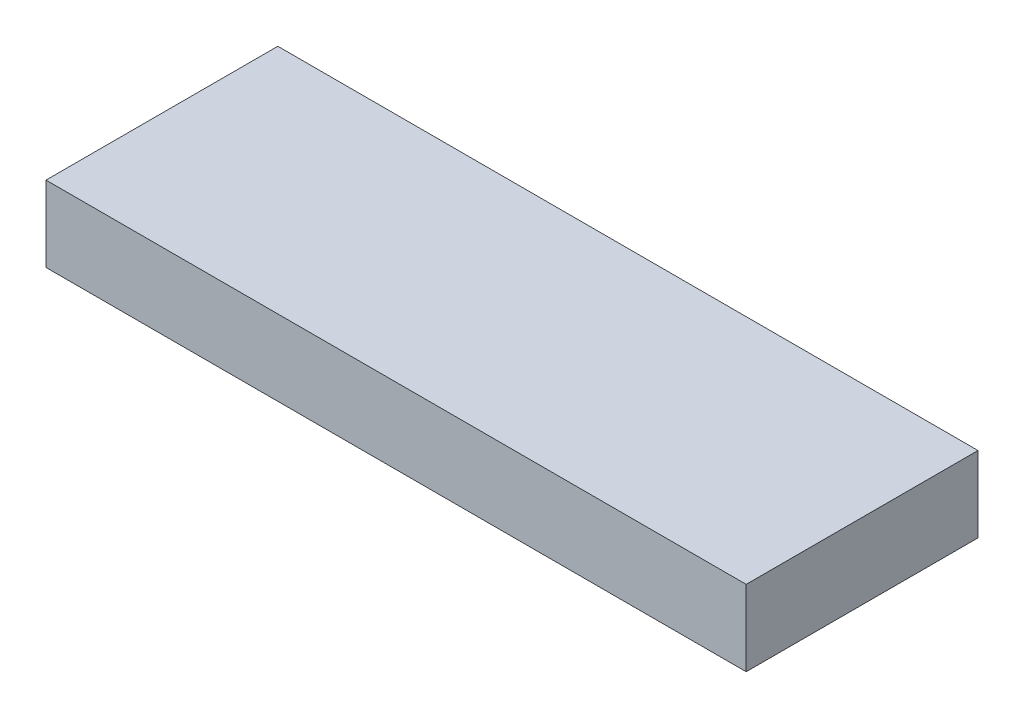
SolidWorks part; units mm, degrees
ref_plane "Front Plane" through (0, 0, 0) normal (0, 0, 1) x (1, 0, 0)
ref_plane "Top Plane" through (0, 0, 0) normal (0, 1, 0) x (1, 0, 0)
ref_plane "Right Plane" through (0, 0, 0) normal (1, 0, 0) x (0, 0, -1)
sketch "Sketch1" plane through (0, 0, 0) normal (0, 1, 0) x (1, 0, 0)
  line L1 (-74, -24.5) -> (74, -24.5)
  line L2 (-74, -24.5) -> (-74, 24.5)
  line L3 (-74, 24.5) -> (74, 24.5)
  line L4 (74, -24.5) -> (74, 24.5)
  line L5 (-74, -24.5) -> (74, 24.5) construction
  line L6 (-74, 24.5) -> (74, -24.5) construction
  point P0 (0, 0)
  dimension "D1" = 148
  dimension "D2" = 49
extrude "Boss-Extrude1" add sketch "Sketch1" along normal blind 16
